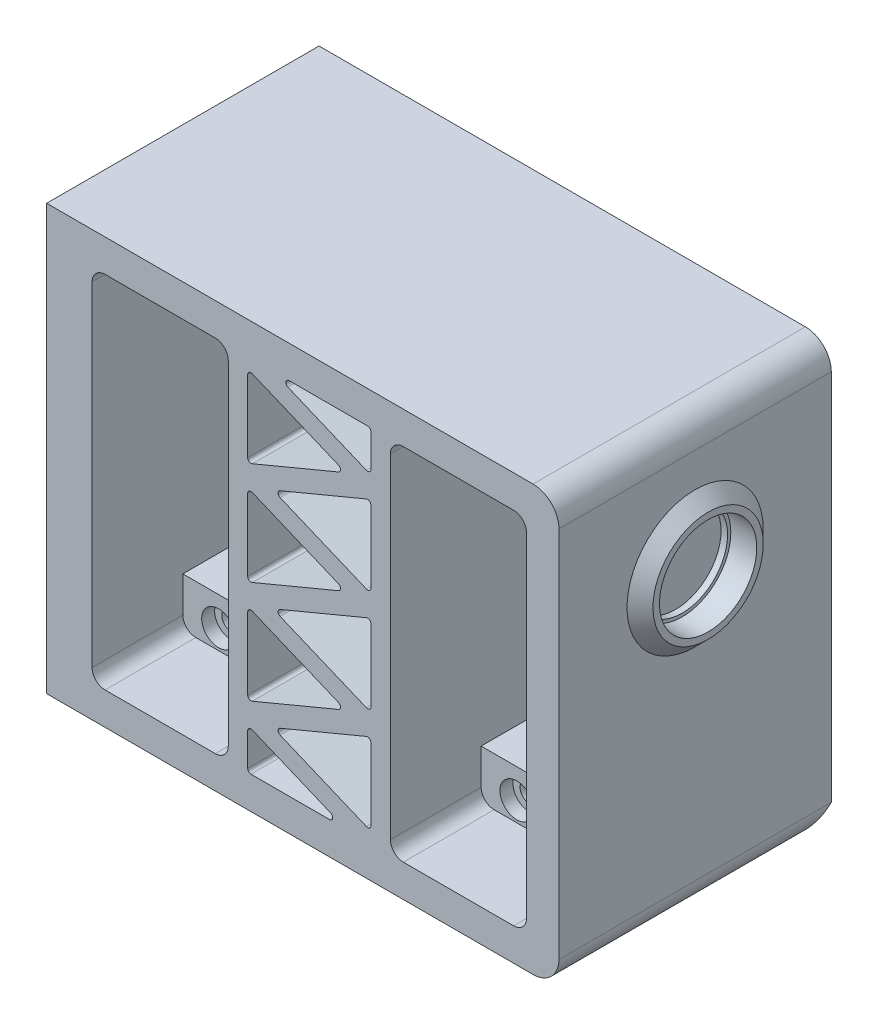
SolidWorks part; units mm, degrees
ref_plane "Front Plane" through (0, 0, 0) normal (0, 0, 1) x (1, 0, 0)
ref_plane "Top Plane" through (0, 0, 0) normal (0, 1, 0) x (1, 0, 0)
ref_plane "Right Plane" through (0, 0, 0) normal (1, 0, 0) x (0, 0, -1)
sketch "Sketch1" plane through (0, 0, 0) normal (0, 0, 1) x (1, 0, 0)
  line L0 (5, 60.5) -> (26, 60.5)
  line L1 (0, 0) -> (77, 0)
  line L2 (0, 0) -> (0, 65.5)
  line L3 (0, 65.5) -> (77, 65.5)
  line L4 (77, 0) -> (77, 65.5)
  line L5 (51, 60.5) -> (72, 60.5)
  line L6 (51, 60.5) -> (51, 5)
  line L7 (51, 5) -> (72, 5)
  line L8 (72, 60.5) -> (72, 5)
  line L9 (5, 60.5) -> (5, 5)
  line L10 (5, 5) -> (26, 5)
  line L12 (26, 60.5) -> (26, 5)
  line L13 (5, 53) -> (26, 53)
  line L14 (51, 53) -> (72, 53)
  line L15 (5, 12.5) -> (26, 12.5)
  line L16 (51, 12.5) -> (72, 12.5)
  line L17 (10.5, 57.5) -> (20.5, 57.5) construction
  line L18 (10.5, 8) -> (20.5, 8) construction
  line L19 (15.5, 57.5) -> (15.5, 8) construction
  line L20 (5, 32.75) -> (26, 32.75) construction
  line L21 (51, 32.75) -> (72, 32.75) construction
  line L22 (61.5, 57.5) -> (61.5, 8) construction
  line L23 (56.5, 57.5) -> (66.5, 57.5) construction
  line L24 (56.5, 8) -> (66.5, 8) construction
  circle A0 centre (10.5, 57.5) radius 1.5
  circle A1 centre (20.5, 57.5) radius 1.5
  circle A2 centre (10.5, 8) radius 1.5
  circle A3 centre (20.5, 8) radius 1.5
  circle A4 centre (56.5, 57.5) radius 1.5
  circle A5 centre (66.5, 57.5) radius 1.5
  circle A6 centre (66.5, 8) radius 1.5
  circle A7 centre (56.5, 8) radius 1.5
  point P33 (15.5, 32.75)
  point P34 (15.5, 32.75)
  point P41 (61.5, 32.75)
  point P42 (61.5, 32.75)
  point P53 (61.5, 8)
  point P55 (61.5, 57.5)
  dimension "D13" = 3
  dimension "D1" = 21
  dimension "D2" = 5
  dimension "D3" = 55.5
  dimension "D4" = 55.5
  dimension "D5" = 21
  dimension "D6" = 5
  dimension "D7" = 5
  dimension "D8" = 25
  dimension "D9" = 5
  dimension "D10" = 7.5
  dimension "D11" = 7.5
  dimension "D12" = 10
  dimension "D15" = 49.5
extrude "Boss-Extrude2" add sketch "Sketch1" against normal blind 28 contours L1 L4 L3 L2 L5 L8 L7 L6 L0 L12 L10 L9 | L9 L13 L12 L0 | L15 L9 L10 L12 | L16 L6 L7 L8 | L6 L14 L8 L5 | A0 | A1 | A4 | A5 | A6 | A7 | A3 | A2 region at (15.5, 56.676, 0) region at (15.5, 8.824, 0) region at (38.5, 32.75, 0) region at (61.5, 56.676, 0) region at (61.5, 8.824, 0) region at (10.5, 57.5, 0) region at (20.5, 57.5, 0) region at (56.5, 57.5, 0) region at (66.5, 57.5, 0) region at (66.5, 8, 0) region at (56.5, 8, 0)
extrude "Boss-Extrude4" add sketch "Sketch1<4>" along normal blind 14 contours L1 L4 L3 L2 L5 L8 L7 L6 L0 L12 L10 L9 region at (38.5, 32.75, 0)
sketch "Sketch1<4>" plane through (0, 0, 0) normal (0, 0, 1) x (1, 0, 0) same geometry as "Sketch1"
extrude "Cut-Extrude1" cut sketch "Sketch1<5>" against normal blind 12 contours A0 | A2 | A3 | A7 | A6 | A4 | A1 | A5 region at (10.5, 57.5, 0) region at (10.5, 8, 0) region at (20.5, 8, 0) region at (56.5, 57.5, 0) region at (66.5, 8, 0) region at (56.5, 8, 0)
sketch "Sketch1<5>" plane through (0, 0, 0) normal (0, 0, 1) x (1, 0, 0) same geometry as "Sketch1"
sketch "Sketch5" plane through (0, 0, 14) normal (0, 0, 1) x (1, 0, 0)
  line L0 (28.4223, 59.1157) -> (44.105, 52.5714)
  line L1 (26, 5) -> (51, 5)
  line L2 (26, 5) -> (26, 60.5)
  line L3 (26, 60.5) -> (51, 60.5)
  line L4 (51, 5) -> (51, 60.5)
  line L5 (26, 60.5) -> (26, 5) construction
  line L6 (51, 60.5) -> (51, 5) construction
  line L7 (5, 60.5) -> (26, 60.5) construction
  line L8 (5, 5) -> (26, 5) construction
  line L9 (29, 60.5) -> (48, 60.5)
  line L10 (48, 5) -> (48, 60.5)
  line L11 (29, 5) -> (48, 5)
  line L12 (29, 5) -> (29, 60.5)
  line L13 (29, 60.5) -> (48, 52.5714)
  line L14 (48, 52.5714) -> (29, 44.6429)
  line L15 (29, 44.6429) -> (48, 36.7143)
  line L16 (48, 36.7143) -> (29, 28.7857)
  line L17 (29, 28.7857) -> (48, 20.8571)
  line L18 (48, 20.8571) -> (29, 12.9286)
  line L19 (29, 12.9286) -> (48, 5)
  line L20 (44.105, 52.5714) -> (25.105, 44.6429)
  line L21 (25.105, 44.6429) -> (44.105, 36.7143)
  line L22 (44.105, 36.7143) -> (25.105, 28.7857)
  line L23 (25.105, 28.7857) -> (44.105, 20.8571)
  line L24 (44.105, 20.8571) -> (25.105, 12.9286)
  line L25 (25.105, 12.9286) -> (47.4223, 3.6157)
  line L26 (29.5777, 61.8843) -> (51.895, 52.5714)
  line L27 (51.895, 52.5714) -> (32.895, 44.6429)
  line L28 (32.895, 44.6429) -> (51.895, 36.7143)
  line L29 (51.895, 36.7143) -> (32.895, 28.7857)
  line L30 (32.895, 28.7857) -> (51.895, 20.8571)
  line L31 (51.895, 20.8571) -> (32.895, 12.9286)
  line L32 (32.895, 12.9286) -> (48.5777, 6.3843)
  dimension "D2" = 1.5
  dimension "D1" = 3
  dimension "D4" = 3
  dimension "D3" = 1.5
extrude "Cut-Extrude2" cut sketch "Sketch5" against normal through all contours L20 L0 L12 | L9 L26 L10 | L27 L28 L10 | L22 L21 L12 | L29 L30 L10 | L24 L23 L12 | L31 L32 L10 | L25 L12 L11 region at (34.035, 52.5714, 14) region at (42.965, 58.3989, 14) region at (34.035, 36.7143, 14) region at (42.965, 44.6429, 14) region at (42.965, 28.7857, 14) region at (34.035, 20.8571, 14) region at (42.965, 12.9286, 14) region at (34.035, 7.1011, 14)
fillet "Fillet4" radius 0.5 24 edges at (44.105, 5, -7) (29, 11.3032, -7) (29, 5, -7) (48, 6.6254, -7) (48, 19.2318, -7) (32.895, 12.9286, -7) (29, 14.5539, -7) (29, 27.1604, -7) (44.105, 20.8571, -7) (48, 22.4825, -7) (48, 35.0889, -7) (32.895, 28.7857, -7) (44.105, 36.7143, -7) (29, 30.4111, -7) (29, 43.0175, -7) (48, 38.3396, -7) (32.895, 44.6429, -7) (48, 50.9461, -7) (29, 46.2682, -7) (44.105, 52.5714, -7) (29, 58.8746, -7) (48, 54.1968, -7) (48, 60.5, -7) (32.895, 60.5, -7)
sketch "Sketch8" plane through (0, 12.5, 0) normal (0, 1, 0) x (1, 0, 0)
  line L0 (26, 28) -> (26, 0) construction
  line L1 (5, 28) -> (26, 28)
  line L2 (5, 28) -> (5, 8)
  line L3 (5, 8) -> (26, 8)
  line L4 (26, 28) -> (26, 8)
  line L5 (51, 0) -> (72, 0) construction
  line L6 (51, 28) -> (72, 28)
  line L7 (51, 28) -> (51, 8)
  line L8 (51, 8) -> (72, 8)
  line L9 (72, 28) -> (72, 8)
  line L10 (72, 28) -> (72, 0) construction
  dimension "D1" = 8
extrude "Cut-Extrude8" cut sketch "Sketch8" against normal blind 10
ref_plane "Midplane" through (0, 32.75, 0) normal (0, 1, 0) x (1, 0, 0)
ref_plane "Plane2" through (61.5, 0, 0) normal (1, 0, 0) x (0, 0, -1)
ref_plane "Plane3" through (15.5, 0, 0) normal (1, 0, 0) x (0, 0, -1)
mirror "Mirror2" about plane through (0, 32.75, 0) normal (0, 1, 0) of "Cut-Extrude8"
sketch "Sketch13" plane through (0, 0, 0) normal (-1, 0, 0) x (0, 0, 1)
  line L4 (-28, 0) -> (14, 0)
  line L5 (14, 0) -> (14, 65.5)
  line L6 (14, 65.5) -> (-28, 65.5)
  line L7 (-28, 65.5) -> (-28, 0)
  line L8 (-28, 0) -> (14, 0)
  line L9 (14, 0) -> (14, 65.5)
  line L10 (14, 65.5) -> (-28, 65.5)
  line L11 (-28, 65.5) -> (-28, 0)
  dimension "D1" = 0
extrude "Boss-Extrude7" add sketch "Sketch13" along normal blind 2
fillet "Fillet3" radius 2 16 edges at (51, 60.5, 7) (72, 5, 7) (72, 60.5, 7) (51, 5, 7) (5, 5, 7) (26, 5, 7) (26, 60.5, 7) (5, 60.5, 7) (72, 63, -18) (72, 2.5, -18) (51, 2.5, -18) (51, 63, -18) (26, 63, -18) (26, 2.5, -18) (5, 63, -18) (5, 2.5, -18)
sketch "Sketch14" plane through (-2, 0, 0) normal (-1, 0, 0) x (0, 0, 1)
  line L8 (-24, 61.5) -> (-24, 4)
  line L9 (-24, 4) -> (10, 4)
  line L10 (10, 4) -> (10, 61.5)
  line L11 (10, 61.5) -> (-24, 61.5)
  line L12 (-24, 61.5) -> (-24, 4) construction
  line L13 (-24, 4) -> (10, 4) construction
  line L14 (10, 4) -> (10, 61.5) construction
  line L15 (10, 61.5) -> (-24, 61.5) construction
  circle A0 centre (-24, 61.5) radius 1.25
  circle A1 centre (10, 61.5) radius 1.25
  circle A2 centre (10, 4) radius 1.25
  circle A3 centre (-24, 4) radius 1.25
  dimension "D2" = 2.5
  dimension "D1" = 4
extrude "Cut-Extrude9" cut sketch "Sketch14" against normal blind 7
fillet "Fillet7" radius 4 2 edges at (77, 65.5, -7) (77, 0, -7)
sketch "Sketch15" plane through (77, 0, 0) normal (1, 0, 0) x (0, 0, -1)
  line L0 (-14, 32.75) -> (28, 32.75) construction
  line L1 (-14, 4) -> (-14, 61.5) construction
  line L2 (28, 4) -> (28, 61.5) construction
  line L3 (-14, 45.75) -> (28, 45.75) construction
  circle A0 centre (7, 45.75) radius 8.5
  dimension "D2" = 17
  dimension "D1" = 13
extrude "Boss-Extrude8" add sketch "Sketch15" along normal blind 2
sketch "Sketch16" plane through (79, 0, 0) normal (1, 0, 0) x (0, 0, -1)
  circle A0 centre (7, 45.75) radius 7.5
  dimension "D1" = 15
extrude "Cut-Extrude10" cut sketch "Sketch16" against normal blind 4
chamfer "Chamfer1" distance 2 angle 45 1 edges at (77, 45.75, -15.5)
sketch "Sketch17" plane through (75, 0, 0) normal (1, 0, 0) x (0, 0, -1)
  circle A0 centre (7, 45.75) radius 7
  dimension "D1" = 14
extrude "Cut-Extrude11" cut sketch "Sketch17" against normal blind 1
sketch "Sketch18" plane through (0, 0, 0) normal (0, 0, 1) x (1, 0, 0)
  circle A0 centre (10.5, 57.5) radius 2.6
  circle A1 centre (20.5, 57.5) radius 2.6
  circle A2 centre (56.5, 57.5) radius 2.6
  circle A3 centre (66.5, 57.5) radius 2.6
  circle A4 centre (66.5, 8) radius 2.6
  circle A5 centre (56.5, 8) radius 2.6
  circle A6 centre (20.5, 8) radius 2.6
  circle A7 centre (10.5, 8) radius 2.6
  dimension "D1" = 5.2
extrude "Cut-Extrude12" cut sketch "Sketch18" against normal blind 2
sketch "Sketch19" plane through (-2, 0, 0) normal (-1, 0, 0) x (0, 0, 1)
  line L0 (-28, 4) -> (-24, 0)
  line L1 (-28, 65.5) -> (-28, 0) construction
  line L2 (-28, 0) -> (14, 0) construction
  line L3 (-28, 4) -> (-28, 0)
  line L4 (-28, 0) -> (-24, 0)
  dimension "D1" = 4
extrude "Cut-Extrude13" cut sketch "Sketch19" against normal through all
sketch "Sketch21" plane through (0, 0, -8) normal (0, 0, -1) x (-1, 0, 0)
  line L0 (-51, 53) -> (-72, 53) construction
  line L1 (-51, 53) -> (-72, 53) construction
  line L2 (-72, 61) -> (-72, 4.5) construction
  line L3 (-64.75, 59) -> (-58.25, 59)
  line L4 (-64.75, 59) -> (-64.75, 53)
  line L5 (-64.75, 53) -> (-58.25, 53)
  line L6 (-58.25, 59) -> (-58.25, 53)
  line L7 (-72, 61) -> (-72, 4.5)
  line L8 (-72, 32.75) -> (-5, 32.75) construction
  line L9 (-64.75, 12.5) -> (-58.25, 12.5)
  line L10 (-58.25, 6.5) -> (-58.25, 12.5)
  line L11 (-64.75, 6.5) -> (-58.25, 6.5)
  line L12 (-64.75, 6.5) -> (-64.75, 12.5)
  line L13 (-5, 61) -> (-5, 4.5) construction
  line L14 (-5, 61) -> (-5, 4.5)
  line L15 (-38.5, 63.0296) -> (-38.5, 7.8475) construction
  line L16 (-12.25, 6.5) -> (-12.25, 12.5)
  line L17 (-12.25, 6.5) -> (-18.75, 6.5)
  line L18 (-18.75, 6.5) -> (-18.75, 12.5)
  line L19 (-12.25, 12.5) -> (-18.75, 12.5)
  line L20 (-12.25, 53) -> (-18.75, 53)
  line L21 (-18.75, 59) -> (-18.75, 53)
  line L22 (-12.25, 59) -> (-18.75, 59)
  line L23 (-12.25, 59) -> (-12.25, 53)
  point P6 (-61.5, 53)
  point P7 (-61.5, 53)
  point P16 (-38.5, 32.75)
  line M8 (-72, 53) -> (-51, 53)
  dimension "D1" = 6.5
  dimension "D2" = 6
extrude "Cut-Extrude14" cut sketch "Sketch21" against normal offset from surface (5 mm away) 3 contours L6 L3 L4 M8 | L12 L11 L10 L9 | L16 L19 L18 L17 | L23 L22 L21 L20 region at (61.5, 56, -8) region at (61.5, 9.5, -8) region at (15.5, 9.5, -8) region at (15.5, 56, -8) up to face at (23.1, 57.5, 0)
chamfer "Chamfer4" distance 2 angle 45 20 edges at (72, 57, -8) (71.4142, 62.4142, -8) (61.5, 63, -8) (51.5858, 62.4142, -8) (51, 57, -8) (72, 8.5, -8) (71.4142, 3.0858, -8) (61.5, 2.5, -8) (51.5858, 3.0858, -8) (51, 8.5, -8) (26, 8.5, -8) (25.4142, 3.0858, -8) (5, 8.5, -8) (5.5858, 3.0858, -8) (15.5, 2.5, -8) (26, 57, -8) (25.4142, 62.4142, -8) (5, 57, -8) (5.5858, 62.4142, -8) (15.5, 63, -8)
